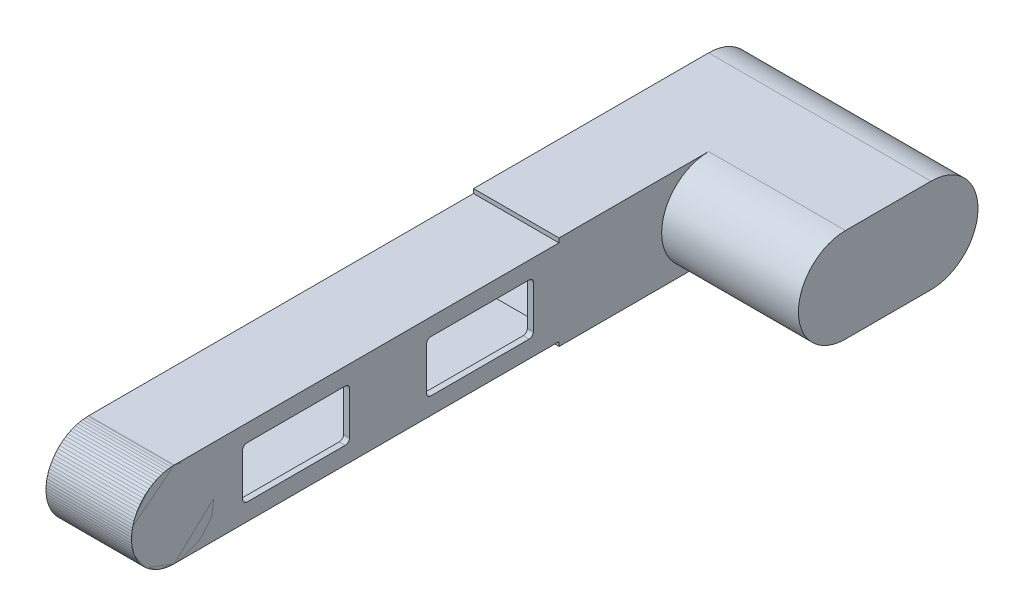
SolidWorks part; units mm, degrees
material "Cast Stainless Steel"
ref_plane "Front Plane" through (0, 0, 0) normal (0, 0, 1) x (1, 0, 0)
ref_plane "Top Plane" through (0, 0, 0) normal (0, 1, 0) x (1, 0, 0)
ref_plane "Right Plane" through (0, 0, 0) normal (1, 0, 0) x (0, 0, -1)
sketch "Sketch1" plane through (0, 0, 0) normal (1, 0, 0) x (0, 0, -1)
  line L0 (0, 0) -> (-500, 0) construction
  line L5 (-500, 50) -> (-50, 50)
  line L6 (50, -55) -> (-50, -55)
  line L7 (50, -55) -> (50, 55)
  line L8 (50, 55) -> (-50, 55)
  line L9 (-50, -55) -> (-50, 55)
  line L10 (50, -55) -> (-50, 55) construction
  line L11 (50, 55) -> (-50, -55) construction
  line L12 (-500, -50) -> (-50, -50)
  line L13 (0, 0) -> (280, 0)
  line L15 (280, 0) -> (50, 0)
  line L16 (280, 0) -> (280, 55)
  line L17 (280, 55) -> (50, 55)
  line L18 (50, 0) -> (50, 55)
  line L19 (280, 0) -> (50, 0)
  line L20 (280, 0) -> (280, -55)
  line L21 (280, -55) -> (50, -55)
  line L22 (50, 0) -> (50, -55)
  circle A0 centre (-500, 0) radius 50
  dimension "D1" = 100
  dimension "D2" = 110
  dimension "D3" = 100
  dimension "D4" = 500
  dimension "D5" = 280
extrude "Boss-Extrude1" add sketch "Sketch1" along normal blind 100 contours A0 L9 | A0 | L9 L6 L7 L8 | L21 L20 L13 L7 | L16 L17 L7 L13 region at (0, 0, 255.5167) region at (0, 0, 500) region at (0, 52.5, 48.5134) region at (0, 27.5, -165) region at (0, -27.5, -165)
sketch "Sketch2" plane through (0, 55, 0) normal (0, 1, 0) x (1, 0, 0)
  line L0 (0, 280) -> (260, 280)
  line L1 (260, 280) -> (260, 70)
  line L2 (260, 70) -> (100, 70)
  line L4 (0, 280) -> (0, -50)
  line L5 (0, -50) -> (100, -50)
  line L6 (100, -50) -> (100, 280)
  line L7 (100, 280) -> (0, 280)
  line L8 (0, 280) -> (0, -50)
  line L10 (100, -50) -> (100, 280)
  line L11 (100, 280) -> (0, 280)
  line L15 (0, -50) -> (100, -50)
  line M9 (100, -50) -> (100, 280)
  dimension "D2" = 260
  dimension "D3" = 210
  dimension "D1" = 0
extrude "Boss-Extrude2" add sketch "Sketch2" against normal up to surface (110 mm away) contours L2 L1 L0 M9 region at (180, 55, -175) up to face at (50, -55, -115)
sketch "Sketch3" plane through (260, 0, 0) normal (1, 0, 0) x (0, 0, -1)
  line L4 (70, -55) -> (280, -55)
  line L5 (280, -55) -> (280, 55)
  line L6 (280, 55) -> (70, 55)
  line L7 (70, 55) -> (70, -55)
  line L8 (70, -55) -> (280, -55)
  line L9 (280, -55) -> (280, 55)
  line L10 (280, 55) -> (70, 55)
  line L11 (70, 55) -> (70, -55)
  circle A0 centre (125, 0) radius 55
  circle A1 centre (225, 0) radius 55
  line M5 (70, -55) -> (280, -55)
  line M6 (280, -55) -> (280, 55)
  line M7 (280, 55) -> (70, 55)
  line M8 (70, 55) -> (70, -55)
  dimension "D1" = 0
extrude "Cut-Extrude1" cut sketch "Sketch3" against normal up to surface (260 mm away) contours A1 L9 M7 | A1 M5 M6 region at (260, -42.7148, -267.7148) region at (260, 42.7148, -267.7148) up to face at (0, 0, 86.25)
extrude "Cut-Extrude2" cut sketch "Sketch3<3>" against normal up to surface (160 mm away) contours A0 L10 M8 | A0 L11 M5 region at (260, -42.7148, -82.2852) region at (260, 42.7148, -82.2852) up to face at (100, 0, 138.75)
sketch "Sketch3<3>" plane through (260, 0, 0) normal (1, 0, 0) x (0, 0, -1) same geometry as "Sketch3"
extrude "Boss-Extrude3" add sketch "Sketch1<3>" along normal blind 100 separate body contours A0 region at (0, 0, 500)
sketch "Sketch1<3>" plane through (0, 0, 0) normal (1, 0, 0) x (0, 0, -1) same geometry as "Sketch1"
ref_plane "Plane1" through (-27.37, 0, 0) normal (-1, 0, 0) x (0, 0, 1)
sketch "Sketch11" plane through (-27.37, 0, 0) normal (-1, 0, 0) x (0, 0, 1)
  point P0 (0, 0)
sketch "Sketch12" plane through (0, 0, 0) normal (-1, 0, 0) x (0, 0, 1)
  line L0 (500, 0) -> (-225, 0) construction
  line L1 (85, 30) -> (200, 30)
  line L2 (80, 25) -> (80, -25)
  line L3 (85, -30) -> (200, -30)
  line L4 (205, 25) -> (205, -25)
  line L5 (250, 30) -> (250, -35.6293) construction
  line L6 (-225, -55) -> (50, -55)
  line L7 (50, -55) -> (50, -50)
  line L8 (50, -50) -> (500, -50)
  line L9 (500, 50) -> (50, 50)
  line L10 (50, 50) -> (50, 55)
  line L11 (50, 55) -> (-225, 55)
  line L12 (-225, -55) -> (50, -55)
  line L13 (50, -55) -> (50, -50)
  line L14 (50, -50) -> (500, -50)
  line L15 (500, 50) -> (50, 50)
  line L16 (50, 50) -> (50, 55)
  line L17 (50, 55) -> (-225, 55)
  line L22 (415, -30) -> (300, -30)
  line L23 (420, 25) -> (420, -25)
  line L24 (295, 25) -> (295, -25)
  line L25 (415, 30) -> (300, 30)
  arc A0 (415, 30) -> (420, 25) centre (415, 25) cw
  arc A1 (415, -30) -> (420, -25) centre (415, -25) ccw
  arc A2 (-225, 55) -> (-225, -55) centre (-225, 0) ccw
  arc A3 (500, -50) -> (500, 50) centre (500, 0) ccw
  arc A4 (-225, 55) -> (-225, -55) centre (-225, 0) ccw
  arc A5 (500, -50) -> (500, 50) centre (500, 0) ccw
  arc A6 (295, 25) -> (300, 30) centre (300, 25) cw
  arc A7 (295, -25) -> (300, -30) centre (300, -25) ccw
  arc A8 (205, 25) -> (200, 30) centre (200, 25) ccw
  arc A9 (205, -25) -> (200, -30) centre (200, -25) cw
  arc A10 (85, 30) -> (80, 25) centre (85, 25) ccw
  arc A11 (80, -25) -> (85, -30) centre (85, -25) ccw
  point P22 (420, 30)
  point P25 (420, -30)
  point P28 (295, 30)
  point P31 (295, -30)
  point P36 (205, 30)
  point P39 (205, -30)
  point P42 (80, 30)
  point P45 (80, -30)
  dimension "D6" = 5
  dimension "D2" = 125
  dimension "D3" = 60
  dimension "D4" = 80
  dimension "D5" = 45
  dimension "D1" = 0
extrude "Cut-Extrude3" cut sketch "Sketch12" against normal up to surface (100 mm away) contours L4 L1 L2 L3 | L23 L25 L24 L22 region at (0, 0, 142.5) region at (0, 0, 357.5) up to face at (100, 0, 131.875)
sketch "Sketch13" plane through (100, 0, 0) normal (1, 0, 0) x (0, 0, -1)
  line L0 (-50, -48) -> (125, -48)
  line L1 (125, -48) -> (225, -48)
  line L2 (125, -55) -> (225, -55)
  line L3 (225, 55) -> (125, 55)
  line L4 (125, -55) -> (225, -55)
  line L5 (225, 55) -> (125, 55)
  line L6 (-50, -55) -> (125, -55)
  line L7 (125, 55) -> (-50, 55)
  line L8 (-50, 55) -> (-50, 50)
  line L9 (-50, 50) -> (-500, 50)
  line L10 (-500, -50) -> (-50, -50)
  line L11 (-50, -50) -> (-50, -55)
  line L12 (-50, -55) -> (125, -55)
  line L13 (125, 55) -> (-50, 55)
  line L14 (-50, 55) -> (-50, 50)
  line L15 (-50, 50) -> (-500, 50)
  line L16 (-500, -50) -> (-50, -50)
  line L17 (-50, -50) -> (-50, -55)
  line L18 (225, 48) -> (125, 48)
  line L19 (125, 48) -> (-50, 48)
  line L20 (-43, 55) -> (-43, 50)
  line L21 (-50, 43) -> (-500, 43)
  line L22 (-50, -55) -> (225, -55)
  line L23 (-50, -50) -> (-50, -55)
  line L24 (-500, -50) -> (-50, -50)
  line L25 (-50, 50) -> (-500, 50)
  line L26 (-50, 55) -> (-50, 50)
  line L27 (225, 55) -> (-50, 55)
  line L28 (-50, -55) -> (225, -55)
  line L29 (-50, -50) -> (-50, -55)
  line L30 (-500, -50) -> (-50, -50)
  line L31 (-50, 50) -> (-500, 50)
  line L32 (-50, 55) -> (-50, 50)
  line L33 (225, 55) -> (-50, 55)
  line L34 (-500, -43) -> (-50, -43)
  line L35 (-43, -50) -> (-43, -55)
  line L36 (-50, -48) -> (225, -48)
  line L37 (225, 48) -> (-50, 48)
  line L38 (-43, -50) -> (-43, -55)
  line L39 (-500, -43) -> (-50, -43)
  line L40 (-50, 43) -> (-500, 43)
  line L41 (-43, 55) -> (-43, 50)
  line L42 (-50, -48) -> (-50, -43)
  line L43 (-50, 43) -> (-50, 48)
  arc A0 (225, -48) -> (225, 48) centre (225, 0) ccw
  arc A1 (225, -48) -> (225, 48) centre (225, 0) ccw
  arc A2 (125, 55) -> (125, -55) centre (125, 0) ccw
  arc A3 (-500, 50) -> (-500, -50) centre (-500, 0) ccw
  arc A5 (-500, 50) -> (-500, -50) centre (-500, 0) ccw
  arc A6 (125, 55) -> (125, -55) centre (125, 0) ccw
  arc A7 (225, -55) -> (225, 55) centre (225, 0) ccw
  arc A8 (-500, 43) -> (-500, -43) centre (-500, 0) ccw
  arc A9 (225, -55) -> (225, 55) centre (225, 0) ccw
  arc A10 (225, -55) -> (225, 55) centre (225, 0) ccw
  arc A11 (-500, 50) -> (-500, -50) centre (-500, 0) ccw
  arc A12 (225, -55) -> (225, 55) centre (225, 0) ccw
  arc A13 (-500, 50) -> (-500, -50) centre (-500, 0) ccw
  arc A14 (-500, 43) -> (-500, -43) centre (-500, 0) ccw
  line M21 (-415, 30) -> (-300, 30)
  line M22 (-295, 25) -> (-295, -25)
  line M23 (-300, -30) -> (-415, -30)
  line M24 (-420, -25) -> (-420, 25)
  arc M26 (125, -55) -> (125, 55) centre (125, 0) cw
  line M33 (-85, -30) -> (-200, -30)
  line M34 (-205, -25) -> (-205, 25)
  line M35 (-200, 30) -> (-85, 30)
  line M36 (-80, 25) -> (-80, -25)
  dimension "D1" = 0
  dimension "D2" = 0
  dimension "D3" = 0
  dimension "D4" = 7
extrude "Cut-Extrude4" cut sketch "Sketch13" against normal offset from surface (86 mm away) 7 from offset 7 contours L21 A8 L34 L42 L0 L19 L43 M26 M36 M33 M34 M35 M24 M21 M22 M23 | L1 A0 L18 L19 L0 M26 region at (100, 0, 222.0795) region at (100, 0, -170.5672) up to face at (0, 0, 142.5) offset against normal yes
